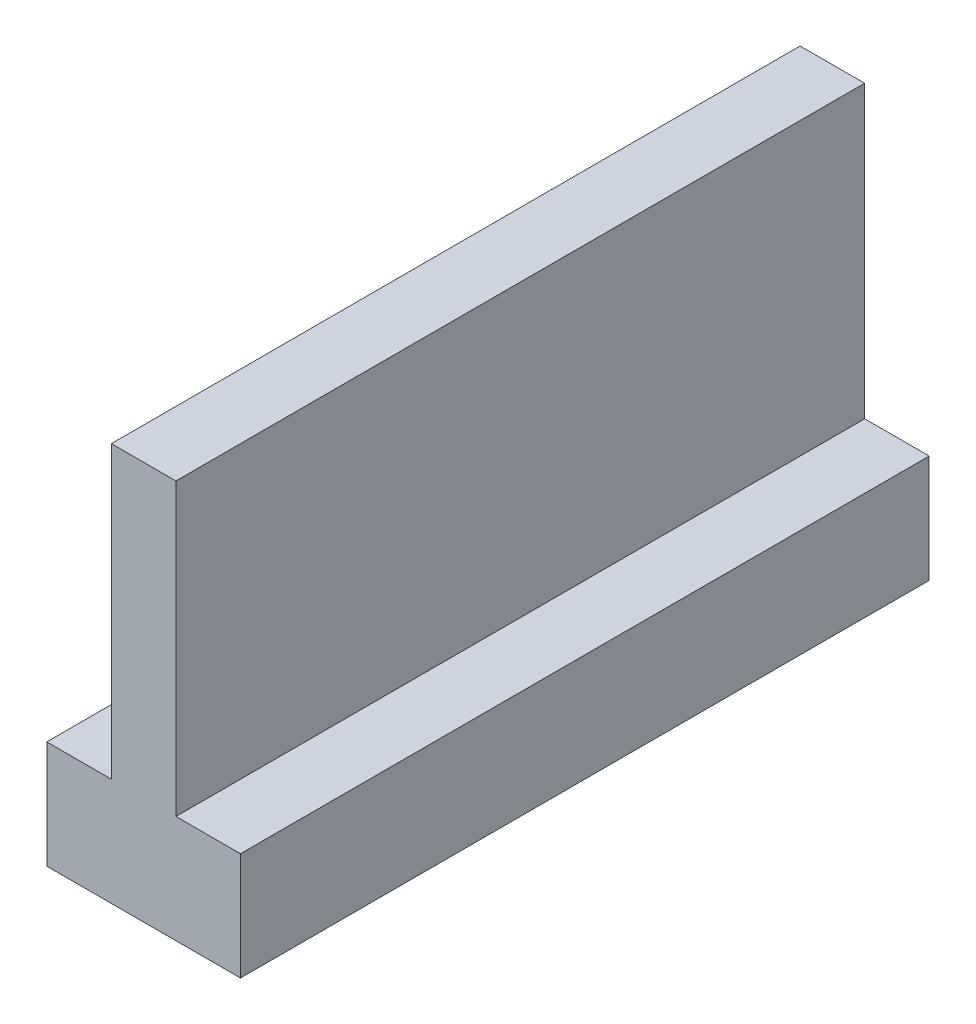
SolidWorks part; units mm, degrees
ref_plane "Front Plane" through (0, 0, 0) normal (0, 0, 1) x (1, 0, 0)
ref_plane "Top Plane" through (0, 0, 0) normal (0, 1, 0) x (1, 0, 0)
ref_plane "Right Plane" through (0, 0, 0) normal (1, 0, 0) x (0, 0, -1)
sketch "Sketch2" plane through (0, 0, 0) normal (0, 0, 1) x (1, 0, 0)
  line L0 (0, 0) -> (0, 10)
  line L1 (0, 10) -> (6, 10)
  line L2 (6, 10) -> (6, 37)
  line L8 (12, 37) -> (12, 10)
  line L9 (12, 10) -> (18, 10)
  line L10 (18, 10) -> (18, 0)
  line L11 (18, 0) -> (0, 0)
  line L12 (9, 0) -> (9, 37) construction
  line L13 (6, 37) -> (12, 37)
  dimension "D1" = 18
  dimension "D2" = 27
  dimension "D3" = 6
  dimension "D4" = 10
extrude "Boss-Extrude2" add sketch "Sketch2" along normal blind 64
